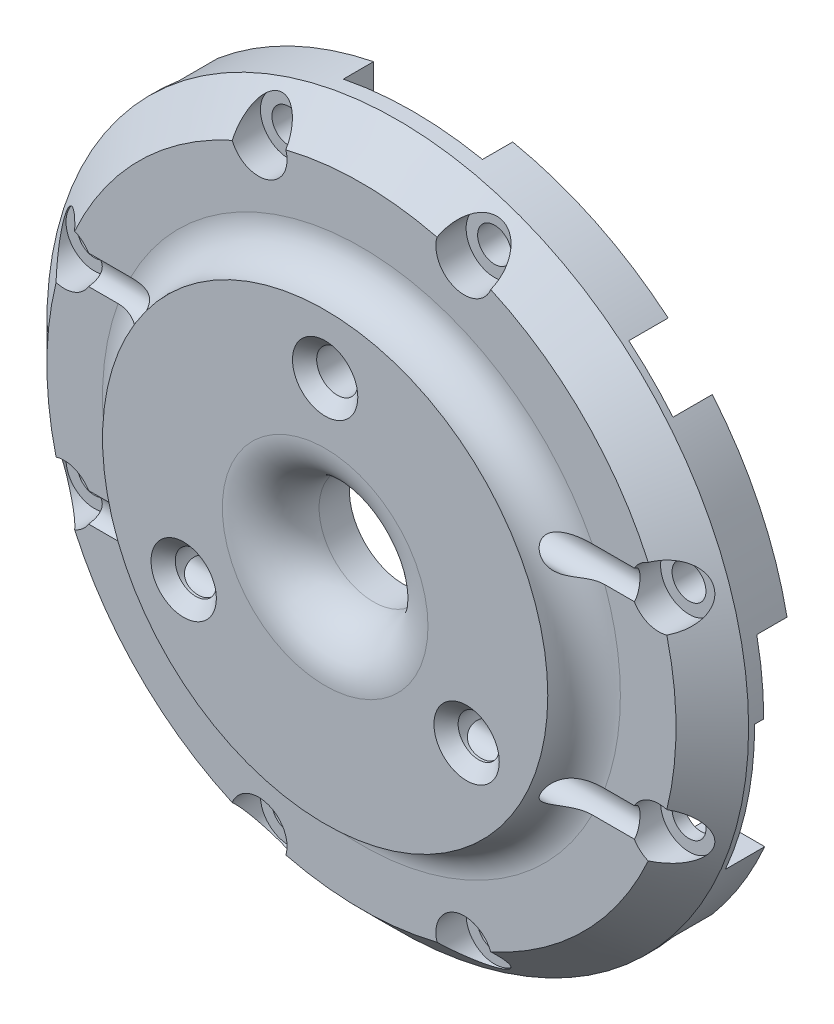
SolidWorks part; units mm, degrees
ref_plane "Front Plane" through (0, 0, 0) normal (0, 0, 1) x (1, 0, 0)
ref_plane "Top Plane" through (0, 0, 0) normal (0, 1, 0) x (1, 0, 0)
ref_plane "Right Plane" through (0, 0, 0) normal (1, 0, 0) x (0, 0, -1)
sketch "Sketch1" plane through (0, 0, 0) normal (0, 0, 1) x (1, 0, 0)
  circle A0 centre (0, 0) radius 29
  dimension "D1" = 58
extrude "Boss-Extrude1" add sketch "Sketch1" along normal blind 6.75
sketch "Sketch3" plane through (0, 0, 0) normal (0, 0, -1) x (-1, 0, 0)
  line L1 (-22.25, -22.25) -> (22.25, -22.25)
  line L2 (-22.25, -22.25) -> (-22.25, 22.25)
  line L3 (-22.25, 22.25) -> (22.25, 22.25)
  line L4 (22.25, -22.25) -> (22.25, 22.25)
  line L5 (-22.25, -22.25) -> (22.25, 22.25) construction
  line L6 (-22.25, 22.25) -> (22.25, -22.25) construction
  point P0 (0, 0)
  dimension "D1" = 44.5
extrude "Cut-Extrude1" cut sketch "Sketch3" against normal blind 3.25
sketch "Sketch4" plane through (0, 0, 6.75) normal (0, 0, 1) x (1, 0, 0)
  circle A0 centre (0, 0) radius 18.4
  dimension "D1" = 36.8
extrude "Boss-Extrude2" add sketch "Sketch4" along normal blind 3
fillet "Fillet1" radius 3 1 edges at (18.4, 0, 6.75)
sketch "Sketch5" plane through (0, 0, 9.75) normal (0, 0, 1) x (1, 0, 0)
  line L0 (-11.6913, -6.75) -> (0, 13.5) construction
  line L1 (0, 13.5) -> (11.6913, -6.75) construction
  line L2 (11.6913, -6.75) -> (-11.6913, -6.75) construction
  circle A2 centre (0, 0) radius 13.5 construction
  circle A3 centre (0, 13.5) radius 1.7
  circle A4 centre (11.6913, -6.75) radius 1.7
  circle A5 centre (-11.6913, -6.75) radius 1.7
  dimension "D1" = 3.4
  dimension "D2" = 27
extrude "Cut-Extrude2" cut sketch "Sketch5" against normal through all
sketch "Sketch7" plane through (0, 0, 3.25) normal (0, 0, -1) x (-1, 0, 0)
  circle A0 centre (-11.6913, -6.75) radius 3.25
  circle A1 centre (11.6913, -6.75) radius 3.25
  circle A2 centre (0, 13.5) radius 3.25
  dimension "D1" = 6.5
extrude "Cut-Extrude3" cut sketch "Sketch7" against normal blind 2
chamfer "Chamfer2" distance 3 angle 45 1 edges at (29, 0, 6.75)
sketch "Sketch9" plane through (0, 0, 0) normal (1, 0, 0) x (0, 0, -1)
  line L0 (-26.5723, 0) -> (15.7273, 0) construction
  line L2 (-6.75, 21.4) -> (-6.75, -21.4) construction
  circle A0 centre (-7.25, 8.5) radius 1.3
  circle A1 centre (-7.25, -8.5) radius 1.3
  dimension "D1" = 2.6
  dimension "D2" = 17
  dimension "D3" = 0.5
extrude "Cut-Extrude5" cut sketch "Sketch9" against normal through all both and the other way through all
sketch "Sketch10" plane through (0, 0, 0) normal (0, 0, -1) x (-1, 0, 0)
  line L0 (5.75, -22.0007) -> (5.75, -34.0342)
  line L1 (22.0007, 5.75) -> (34.0342, 5.75)
  line L2 (22.0007, 5.75) -> (22.0007, -5.75)
  line L3 (22.0007, -5.75) -> (34.0342, -5.75)
  line L4 (34.0342, 5.75) -> (34.0342, -5.75)
  line L5 (5.75, -22.0007) -> (-5.75, -22.0007)
  line L6 (-5.75, -22.0007) -> (-5.75, -34.0342)
  line L7 (5.75, -34.0342) -> (-5.75, -34.0342)
  line L8 (-22.0007, -5.75) -> (-34.0342, -5.75)
  line L9 (-22.0007, -5.75) -> (-22.0007, 5.75)
  line L10 (-22.0007, 5.75) -> (-34.0342, 5.75)
  line L11 (-34.0342, -5.75) -> (-34.0342, 5.75)
  line L12 (-5.75, 22.0007) -> (-5.75, 34.0342)
  line L13 (-5.75, 22.0007) -> (5.75, 22.0007)
  line L14 (5.75, 22.0007) -> (5.75, 34.0342)
  line L15 (-5.75, 34.0342) -> (5.75, 34.0342)
  point P4 (22.0007, 0)
  point P21 (0, 0)
  dimension "D1" = 11.5
  dimension "D2" = 4
extrude "Cut-Extrude6" cut sketch "Sketch10" against normal blind 2.5
sketch "Sketch11" plane through (0, 0, 0) normal (0, 0, -1) x (-1, 0, 0)
  line L0 (-36.6727, 0) -> (0, 0) construction
  circle A0 centre (0, 0) radius 26 construction
  circle A1 centre (-24.5713, 8.5) radius 1.4
  circle A2 centre (-24.5713, -8.5) radius 1.4
  circle A3 centre (-8.5, 24.5713) radius 1.4
  circle A4 centre (8.5, 24.5713) radius 1.4
  circle A5 centre (24.5713, 8.5) radius 1.4
  circle A6 centre (24.5713, -8.5) radius 1.4
  circle A7 centre (8.5, -24.5713) radius 1.4
  circle A8 centre (-8.5, -24.5713) radius 1.4
  point P23 (0, 0)
  dimension "D1" = 52
  dimension "D3" = 2.8
  dimension "D4" = 17
  dimension "D2" = 4
extrude "Cut-Extrude7" cut sketch "Sketch11" against normal through all
sketch "Sketch12" plane through (0, 0, 6.75) normal (0, 0, 1) x (1, 0, 0)
  circle A0 centre (-24.5713, 8.5) radius 2.35
  circle A1 centre (-24.5713, -8.5) radius 2.35
  circle A2 centre (8.5, 24.5713) radius 2.35
  circle A3 centre (-8.5, 24.5713) radius 2.35
  circle A4 centre (24.5713, -8.5) radius 2.35
  circle A5 centre (24.5713, 8.5) radius 2.35
  circle A6 centre (-8.5, -24.5713) radius 2.35
  circle A7 centre (8.5, -24.5713) radius 2.35
  point P21 (0, 0)
  dimension "D1" = 4.7
  dimension "D2" = 4
extrude "Cut-Extrude8" cut sketch "Sketch12" against normal blind 2.5
sketch "Sketch13" plane through (0, 0, 3.25) normal (0, 0, -1) x (-1, 0, 0)
  line L0 (-22.25, 18.5994) -> (-22.25, -18.5994) construction
  line L1 (-22.15, 14.75) -> (-15.65, 14.75)
  line L2 (-22.15, 14.75) -> (-22.15, 8.25)
  line L3 (-22.15, 8.25) -> (-15.65, 8.25)
  line L4 (-15.65, 14.75) -> (-15.65, 8.25)
  line L5 (18.5994, 22.25) -> (-18.5994, 22.25) construction
  line L6 (14.75, 22.15) -> (14.75, 15.65)
  line L7 (14.75, 22.15) -> (8.25, 22.15)
  line L8 (8.25, 22.15) -> (8.25, 15.65)
  line L9 (14.75, 15.65) -> (8.25, 15.65)
  line L10 (22.15, -14.75) -> (15.65, -14.75)
  line L11 (22.15, -14.75) -> (22.15, -8.25)
  line L12 (22.15, -8.25) -> (15.65, -8.25)
  line L13 (15.65, -14.75) -> (15.65, -8.25)
  line L14 (-14.75, -22.15) -> (-14.75, -15.65)
  line L15 (-14.75, -22.15) -> (-8.25, -22.15)
  line L16 (-8.25, -22.15) -> (-8.25, -15.65)
  line L17 (-14.75, -15.65) -> (-8.25, -15.65)
  point P23 (0, 0)
  dimension "D1" = 0.1
  dimension "D2" = 7.5
  dimension "D4" = 6.5
  dimension "D3" = 4
extrude "Cut-Extrude9" cut sketch "Sketch13" against normal blind 2.25
chamfer "Chamfer5" distance 1 angle 45 12 edges at (-14.75, 18.9, 3.25) (-11.5, 15.65, 3.25) (-8.25, 18.9, 3.25) (14.75, -18.9, 3.25) (11.5, -15.65, 3.25) (8.25, -18.9, 3.25) (-18.9, -8.25, 3.25) (-15.65, -11.5, 3.25) (-18.9, -14.75, 3.25) (18.9, 8.25, 3.25) (15.65, 11.5, 3.25) (18.9, 14.75, 3.25)
sketch "Sketch14" plane through (0, 0, 0) normal (0, 0, -1) x (-1, 0, 0)
  line L1 (-35.1198, 0) -> (-19.2322, 0)
  line L2 (-35.1198, 0) -> (-35.1198, -11.6)
  line L3 (-35.1198, -11.6) -> (-19.2322, -11.6)
  line L4 (-19.2322, 0) -> (-19.2322, -11.6)
  dimension "D1" = 11.6
extrude "Cut-Extrude10" cut sketch "Sketch14" against normal up to surface (3.25 mm away) up to face at (18.4, 11.5, 3.25)
fillet "Fillet2" radius 1.5 3 edges at (-8.5776, -5.8189, 3.25) (8.4413, -6.75, 3.25) (-3.25, 13.5, 3.25)
sketch "Sketch15" plane through (0, 0, 6.75) normal (0, 0, 1) x (1, 0, 0)
  line L0 (0, 0) -> (11.6673, 11.6673) construction
  line L1 (0, 0) -> (36.7921, 0) construction
  circle A0 centre (11.6673, 11.6673) radius 12.5
  circle A1 centre (0, 0) radius 29 construction
  dimension "D2" = 25
  dimension "D1" = 45
sketch "Sketch16" plane through (0, 0, 9.75) normal (0, 0, 1) x (1, 0, 0)
  circle A0 centre (0, 0) radius 4.5
  dimension "D1" = 9
extrude "Cut-Extrude11" cut sketch "Sketch16" against normal through all
fillet "Fillet3" radius 4 1 edges at (4.5, 0, 9.75)
chamfer "Chamfer6" distance 1 angle 45 3 edges at (13.3913, -6.75, 9.75) (-9.9913, -6.75, 9.75) (1.7, 13.5, 9.75)
